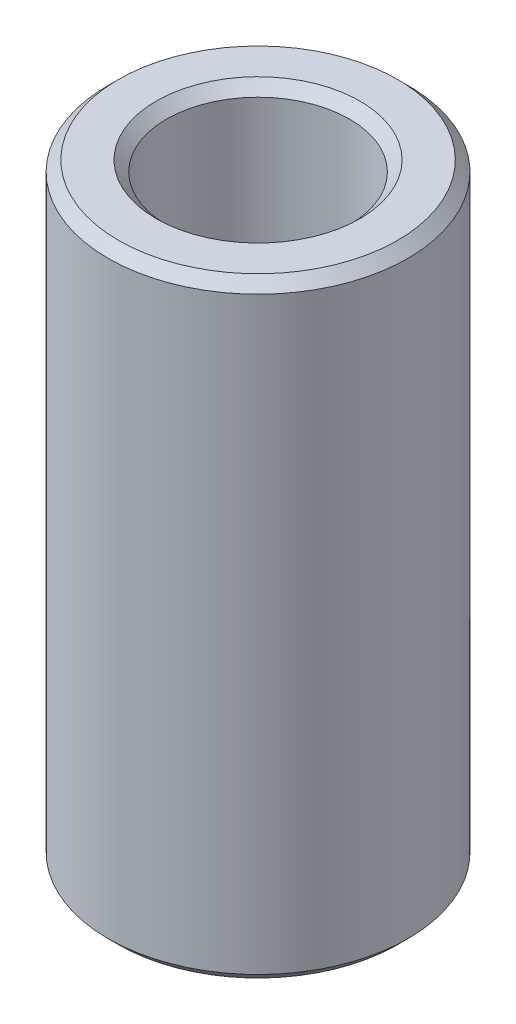
SolidWorks part; units mm, degrees
ref_plane "Front Plane" through (0, 0, 0) normal (0, 0, 1) x (1, 0, 0)
ref_plane "Top Plane" through (0, 0, 0) normal (0, 1, 0) x (1, 0, 0)
ref_plane "Right Plane" through (0, 0, 0) normal (1, 0, 0) x (0, 0, -1)
sketch "Sketch1" plane through (0, 0, 0) normal (0, 1, 0) x (1, 0, 0)
  circle A0 centre (0, 0) radius 7.5
  dimension "SLEEVE_OD" = 15
extrude "Boss-Extrude1" add sketch "Sketch1" along normal blind 30.5232
sketch "Sketch2" plane through (0, 0, 0) normal (0, 1, 0) x (1, 0, 0)
  circle A0 centre (0, 0) radius 4.5781
  dimension "BORE_D" = 9.1562
extrude "Cut-Extrude1" cut sketch "Sketch2" along normal through all
chamfer "Chamfer1" distance 0.5198 angle 45 4 edges at (0, 30.5232, 4.5781) (0, 0, 4.5781) (0, 0, 7.5) (0, 30.5232, 7.5)
